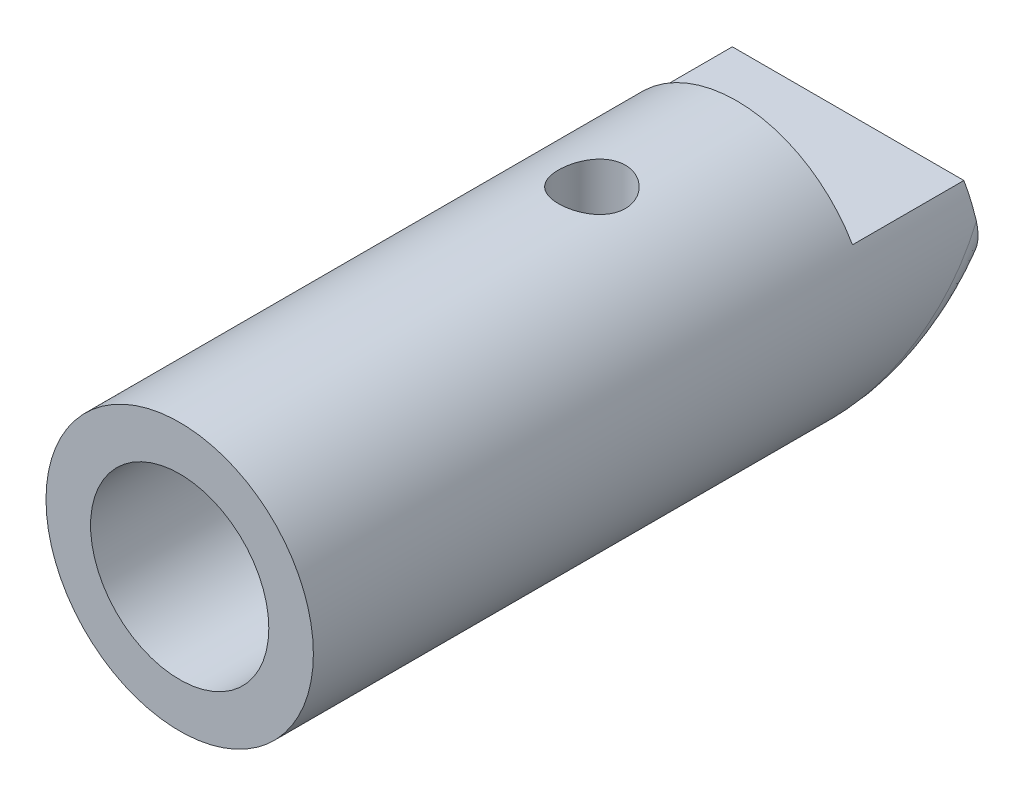
SolidWorks part; units mm, degrees
ref_plane "Front" through (0, 0, 0) normal (0, 0, 1) x (1, 0, 0)
ref_plane "Top" through (0, 0, 0) normal (0, 1, 0) x (1, 0, 0)
ref_plane "Right" through (0, 0, 0) normal (1, 0, 0) x (0, 0, -1)
sketch "Sketch1" plane through (0, 0, 0) normal (0, 0, 1) x (1, 0, 0)
  circle A0 centre (0, 0) radius 6
  dimension "D1" = 12
extrude "Boss-Extrude1" add sketch "Sketch1" along normal blind 30
sketch "Sketch2" plane through (0, 0, 30) normal (0, 0, 1) x (1, 0, 0)
  circle A0 centre (0, 0) radius 4
  dimension "D1" = 8
extrude "Cut-Extrude1" cut sketch "Sketch2" against normal blind 12
sketch "Sketch3" plane through (0, 0, 0) normal (1, 0, 0) x (0, 0, -1)
  line L1 (5, 8.3324) -> (-5, 8.3324)
  line L2 (5, 8.3324) -> (5, 3)
  line L3 (5, 3) -> (-5, 3)
  line L4 (-5, 8.3324) -> (-5, 3)
  line L5 (-30, -6) -> (0, -6) construction
  line L6 (0, -6) -> (0, 6) construction
  dimension "D1" = 9
  dimension "D2" = 5
  dimension "D3" = 10
  dimension "D4" = 5.3324
extrude "Cut-Extrude2" cut sketch "Sketch3" against normal mid plane 12
sketch "Sketch4" plane through (0, 0, 0) normal (1, 0, 0) x (0, 0, -1)
  line L0 (0, 0) -> (-7.6879, -7.6879)
  line L1 (-7.6879, -7.6879) -> (1, -7.6879)
  line L2 (1, -7.6879) -> (1, 1)
  line L3 (0, 0) -> (1, 1)
  line L4 (0, -6) -> (0, 3) construction
  dimension "D1" = 1
  dimension "D2" = 45
  dimension "D3" = 8.6879
extrude "Cut-Extrude3" cut sketch "Sketch4" against normal mid plane 22
fillet "Fillet1" radius 1 1 edges at (0, -6, 6)
ref_plane "Plane1" through (0, 6, 0) normal (0, 1, 0) x (-1, 0, 0)
sketch "Sketch5" plane through (0, 6, 0) normal (0, 1, 0) x (-1, 0, 0)
  line L0 (-5.1962, 5) -> (5.1962, 5) construction
  circle A0 centre (0, 11.5) radius 1.5
  dimension "D2" = 3
  dimension "D1" = 5
extrude "Cut-Extrude4" cut sketch "Sketch5" against normal blind 3
